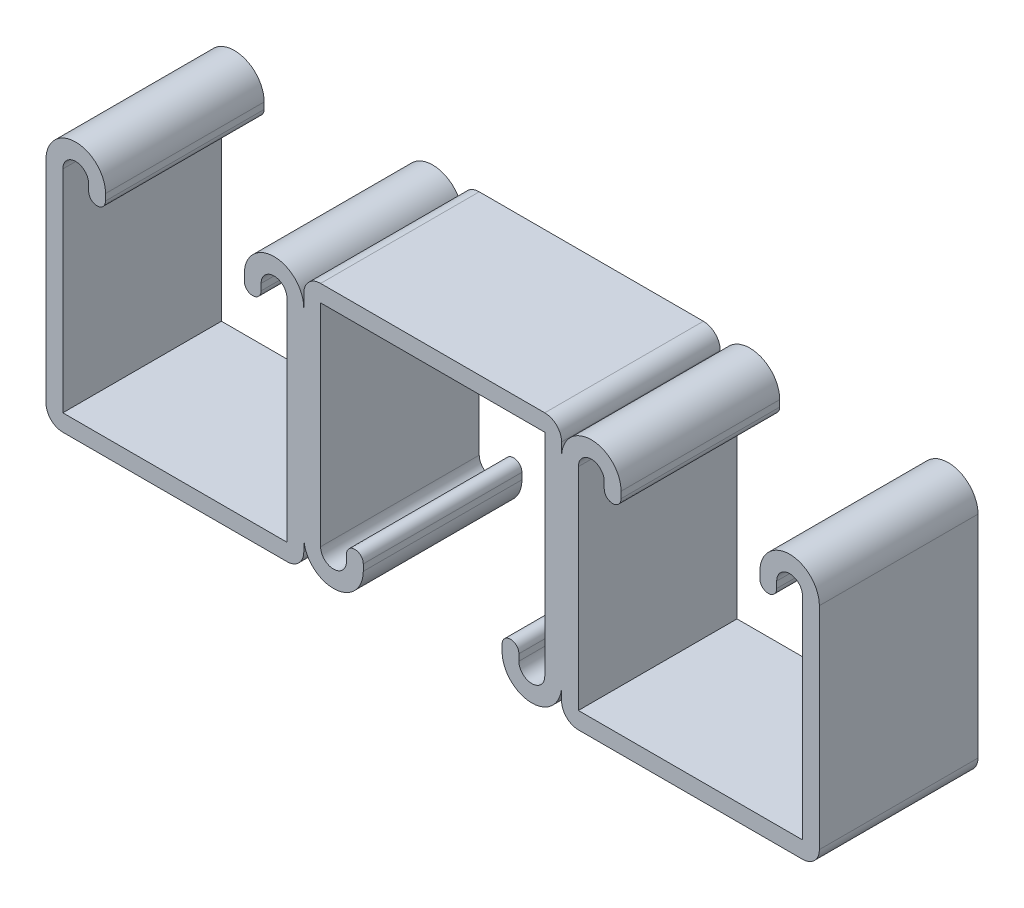
SolidWorks part; units mm, degrees
note: '?' marks a value the reader was unsure of.
ref_plane "Plane1" through (0, 0, 0) normal (0, 0, 1) x (1, 0, 0)
ref_plane "Plane2" through (0, 0, 0) normal (0, 1, 0) x (1, 0, 0)
ref_plane "Plane3" through (0, 0, 0) normal (1, 0, 0) x (0, 0, -1)
sketch "Sketch1" plane through (0, 0, 0) normal (0, 0, 1) x (1, 0, 0)
  line L0 (-41.275, 15.875) -> (-41.275, -17.9451)
  line L1 (-38.5826, -20.6375) -> (-2.6924, -20.6375)
  line L2 (0, -17.9451) -> (0, 15.875)
  line L3 (-9.525, 15.875) -> (-9.525, 14.8399)
  line L4 (-31.75, 15.875) -> (-31.75, 14.8399)
  line L5 (-34.4424, 15.875) -> (-34.4424, 14.8399)
  line L6 (-38.5826, 15.875) -> (-38.5826, -17.9451)
  line L7 (-38.5826, -17.9451) -> (-2.6924, -17.9451)
  line L8 (-2.6924, -17.9451) -> (-2.6924, 15.875)
  line L9 (-6.8326, 15.875) -> (-6.8326, 14.8399)
  line L10 (-44.483, 20.6375) -> (25.4, 20.6375) construction
  line L11 (-36.5125, 13.4937) -> (12.8524, 13.4937) construction
  arc A0 (0, 15.875) -> (-9.525, 15.875) centre (-4.7625, 15.875) ccw
  arc A1 (-41.275, 15.875) -> (-31.75, 15.875) centre (-36.5125, 15.875) cw
  arc A2 (-38.5826, -20.6375) -> (-41.275, -17.9451) centre (-38.5826, -17.9451) cw
  arc A3 (-2.6924, -20.6375) -> (0, -17.9451) centre (-2.6924, -17.9451) ccw
  arc A4 (-38.5826, 15.875) -> (-34.4424, 15.875) centre (-36.5125, 15.875) cw
  arc A5 (-2.6924, 15.875) -> (-6.8326, 15.875) centre (-4.7625, 15.875) ccw
  arc A6 (-9.525, 14.8399) -> (-6.8326, 14.8399) centre (-8.1788, 14.8399) ccw
  arc A7 (-31.75, 14.8399) -> (-34.4424, 14.8399) centre (-33.0962, 14.8399) cw
  dimension "D5" = 20.6375
  dimension "D6" = 9.525
  dimension "D7" = 22.225
  dimension "D8" = 20.6375
  dimension "D9" = 7.1437
extrude "Base-Extrude" add sketch "Sketch1" along normal mid plane 25.4
ref_axis "Axis1" through (0, 0, -50) along (0, 0, 1)?
pattern_circular "CirPattern1" count 2 every 180 about axis through (0, 0, 0) along (0, 0, 1) of "Base-Extrude"
pattern_linear "LPattern1" count 2 spacing 82.55 along (1, 0, 0) of "Base-Extrude"
equation "\"D7@Sketch1\" = \"Width@Sketch1\" - 2 * \"D6@Sketch1\""
equation "\"D1@Sketch1\" = \"gauge@Sketch1\""
